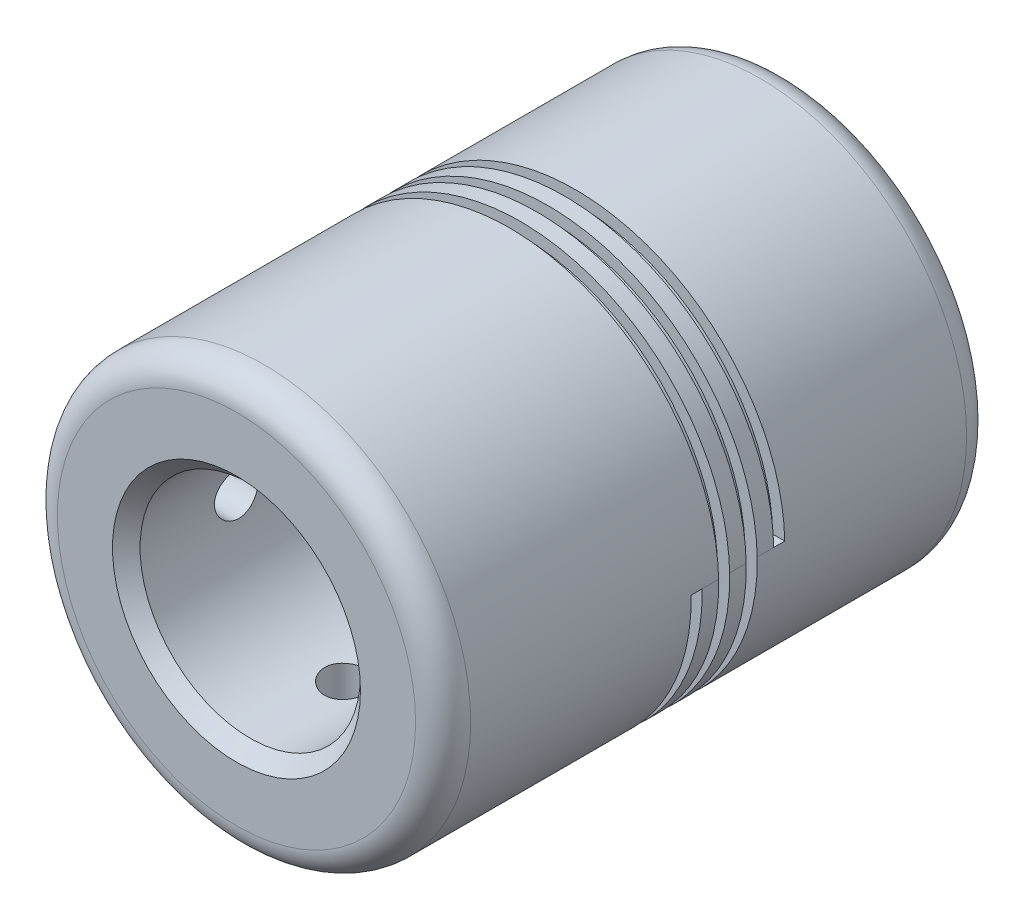
SolidWorks part; units mm, degrees
ref_plane "Piano frontale" through (0, 0, 0) normal (0, 0, 1) x (1, 0, 0)
ref_plane "Piano superiore" through (0, 0, 0) normal (0, 1, 0) x (1, 0, 0)
ref_plane "Piano destro" through (0, 0, 0) normal (1, 0, 0) x (0, 0, -1)
sketch "Schizzo1" plane through (0, 0, 0) normal (0, 0, 1) x (1, 0, 0)
  circle A0 centre (0, 0) radius 7.5
  dimension "D1" = 15
extrude "Estrusione-Estrusione1" add sketch "Schizzo1" along normal blind 20
sketch "Schizzo2" plane through (0, 0, 20) normal (0, 0, 1) x (1, 0, 0)
  circle A0 centre (0, 0) radius 4
  dimension "D1" = 8
extrude "Taglio-Estrusione1" cut sketch "Schizzo2" against normal blind 10
sketch "Schizzo3" plane through (0, 0, 10) normal (0, 0, 1) x (1, 0, 0)
  circle A0 centre (0, 0) radius 2.6
  dimension "D1" = 5.2
extrude "Taglio-Estrusione2" cut sketch "Schizzo3" against normal up to next
fillet "Raccordo1" radius 1 2 edges at (7.5, 0, 20) (7.5, 0, 0)
sketch "Schizzo4" plane through (0, 0, 0) normal (0, 1, 0) x (1, 0, 0)
  line L0 (0, 0) -> (0, -20) construction
  line L1 (-6.5, -20) -> (6.5, -20) construction
  line L2 (-7.5, -10) -> (7.5, -10) construction
  line L3 (-7.5, -1) -> (-7.5, -19) construction
  line L4 (7.5, -19) -> (7.5, -1) construction
  circle A0 centre (0, -4) radius 0.8
  circle A1 centre (0, -16) radius 0.8
  point P13 (0, 0)
  dimension "D1" = 1.6
  dimension "D2" = 6
extrude "Taglio-Estrusione3" cut sketch "Schizzo4" against normal up to surface (7.5 mm away) up to face at (7.5, 0, 19)
ref_axis "Assi1" through (0, 0, 19) along (0, 0, -1)
pattern_circular "RipetizioneCircolare1" count 2 every 90 about axis through (0, 0, 19) along (0, 0, -1) of "Taglio-Estrusione3"
ref_plane "Piano1" through (0, 0, 8) normal (0, 0, -1) x (-1, 0, 0)
sketch "Schizzo5" plane through (0, 0, 8) normal (0, 0, -1) x (-1, 0, 0)
  circle A0 centre (0, 0) radius 7.5
  circle A1 centre (0, 0) radius 7.5 construction
curve "Elica/Spirale1" pitch 1 height 3 radius 7.5 centre (0, 0, 8) axis (0, 0, 1) start towards (1, 0, 0)
sketch "Schizzo6" plane through (0, 0, 0) normal (0, 1, 0) x (1, 0, 0)
  line L0 (7.15, -8) -> (-7.15, -8) construction
  line L1 (7.0642, -8) -> (8.0326, -8)
  line L2 (7.0642, -8) -> (7.0642, -7.6)
  line L3 (7.0642, -7.6) -> (8.0326, -7.6)
  line L4 (8.0326, -8) -> (8.0326, -7.6)
  line L5 (7.5, -19) -> (7.5, -1) construction
  dimension "D1" = 0.4
  dimension "D2" = 0.4358
sweep "Taglia-Sweep1" cut profiles "Schizzo6" path "Elica/Spirale1" align with end faces yes
chamfer "Smusso1" distance 0.5 angle 45 2 edges at (2.6, 0, 0) (4, 0, 20)
